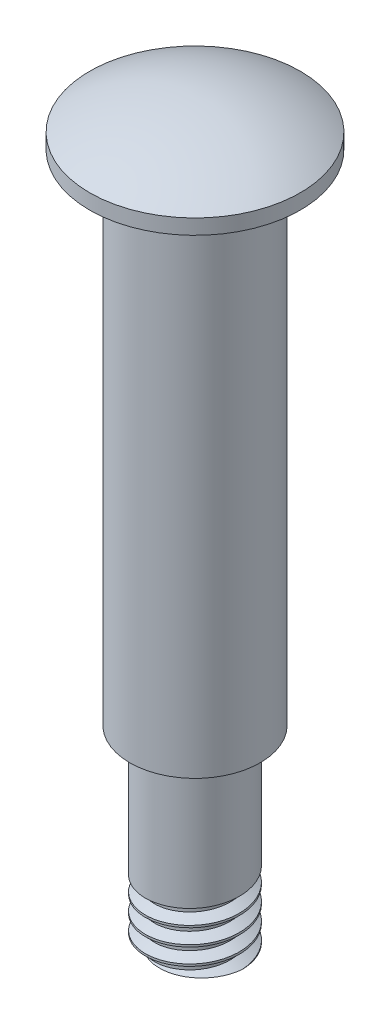
SolidWorks part; units mm, degrees
material "6061-T6 (SS)"
ref_plane "Front Plane" through (0, 0, 0) normal (1, 0, 0) x (0, 1, 0)
ref_plane "Top Plane" through (0, 0, 0) normal (0, 0, 1) x (0, 1, 0)
ref_plane "Right Plane" through (0, 0, 0) normal (0, 1, 0) x (-1, 0, 0)
sketch "Sketch1" plane through (0, 0, 0) normal (1, 0, 0) x (0, 1, 0)
  line L0 (0, 0) -> (-57.9625, 0)
  line L1 (-57.9625, 0) -> (-57.9625, 3.9688)
  line L2 (-57.9625, 3.9688) -> (-42.0875, 3.9688)
  line L3 (-42.0875, 3.9688) -> (-42.0875, 5.5)
  line L4 (-42.0875, 5.5) -> (0, 5.5)
  line L5 (0, 5.5) -> (0, 8.89)
  line L6 (0, 8.89) -> (3.81, 8.89)
  line L7 (3.81, 8.89) -> (3.81, 0)
  line L8 (3.81, 0) -> (0, 0)
  line L9 (-57.9625, -3.9687) -> (-57.9625, 3.9688)
  line L11 (-57.9625, 0) -> (-57.9625, 3.9688) construction
  line L13 (-42.0875, -5.5) -> (-42.0875, 5.5)
  arc A0 (3.81, 0) -> (1.27, 8.89) centre (-13.0175, 0) ccw
  point P15 (-57.9625, 0)
  point P17 (-42.0875, 0)
  dimension "D3" = 8.89
  dimension "D4" = 3.81
  dimension "D5" = 15.875
  dimension "D6" = 90
  dimension "D7" = 42.0875
  dimension "D8" = 3.39
  dimension "D9" = 0
  dimension "D10" = 1.27
  dimension "D2" = 7.9375
  dimension "D11" = 11
  dimension "D12" = 1.5313
revolve "Revolve1" add sketch "Sketch1" angle 360 about L0 region at (0, -18.7121, 2.8609) region at (0, -50.025, 1.9844)
thread "Thread1" pitch 1.4111 method cut profile "Thread Profile2" start angle 0, offset 1.4111, length 6.35, pitch 1.4111, diameter 7.9375
ref_plane "Plane2" through (3.9688, -59.3736, 0) normal (0, 0, 1) x (1, 0, 0)
sketch "Thread Profile2" plane through (3.9688, -59.3736, 0) normal (0, 0, 1) x (1, 0, 0)
  line L0 (0, 0) -> (0, 1.4111) construction
  line L11 (0, 0) -> (0, 1.2347)
  line L12 (0, 1.2347) -> (-0.7638, 0.7937)
  line L13 (-0.7638, 0.7937) -> (-0.7638, 0.441)
  line L15 (-0.7638, 0.441) -> (0, 0)
  line L17 (-0.7638, 0.6174) -> (0, 0.6174) construction
  point P2 (0, 0)
  dimension "Pitch" = 1.4111
  dimension "Profile_Angle" = 60
  dimension "Profile_Land" = 0.3528
  dimension "Profile_Height" = 0.7638
equation "\"D11@Sketch1\"=11mm"
equation "\"nut\"= 0.15"
equation "\"washer\"= 0.0625"
equation "\"wall\"= 0.35"
equation "\"pin support\"= 32.5mm"
equation "\"wall support\"= 0.125"
equation "\"D5@Sketch1\"=\"nut\"+\"washer\"*2+\"wall\""
equation "\"D7@Sketch1\"= \"pin support\" + \"wall support\" - \"washer\" + \"gear\" + \"clearance\""
equation "\"gear\"= 6mm"
equation "\"clearance\"= 2mm"
